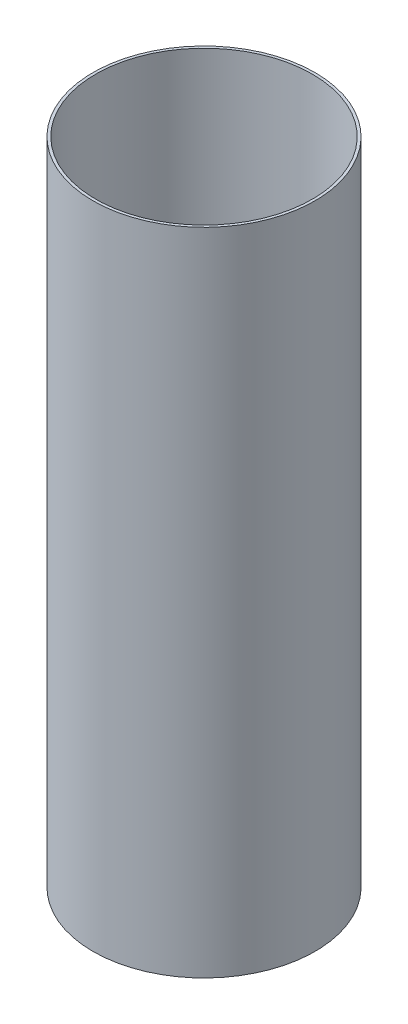
SolidWorks part; units mm, degrees
ref_plane "Front Plane" through (0, 0, 0) normal (0, 0, 1) x (1, 0, 0)
ref_plane "Top Plane" through (0, 0, 0) normal (0, 1, 0) x (1, 0, 0)
ref_plane "Right Plane" through (0, 0, 0) normal (1, 0, 0) x (0, 0, -1)
sketch "Sketch1" plane through (0, 0, 0) normal (0, 1, 0) x (1, 0, 0)
  circle A0 centre (0, 0) radius 50.8
  circle A1 centre (0, 0) radius 52.07
  dimension "D1" = 101.6
  dimension "D2" = 104.14
extrude "Boss-Extrude1" add sketch "Sketch1" along normal blind 304.8
